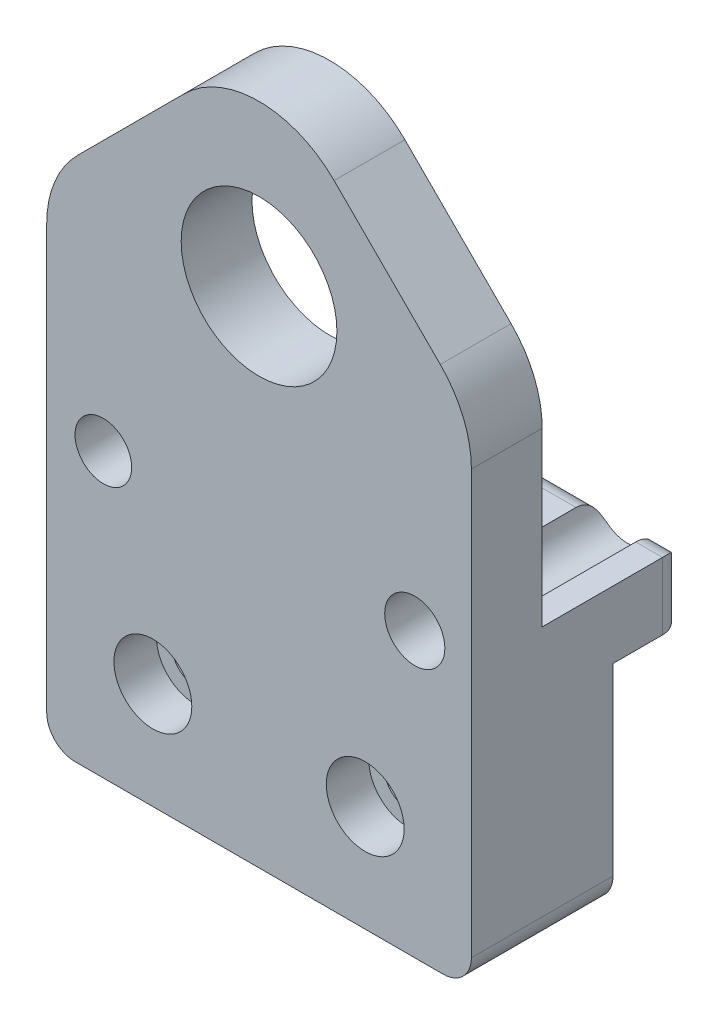
SolidWorks part; units mm, degrees
ref_plane "Front Plane" through (0, 0, 0) normal (0, 0, 1) x (1, 0, 0)
ref_plane "Top Plane" through (0, 0, 0) normal (0, 1, 0) x (1, 0, 0)
ref_plane "Right Plane" through (0, 0, 0) normal (1, 0, 0) x (0, 0, -1)
sketch "Esboço2" plane through (0, 0, 0) normal (0, 0, 1) x (1, 0, 0)
  line L0 (250, 102.2122) -> (250, 76.2122) construction
  line L1 (190, 102.2122) -> (190, 76.2122) construction
  line L2 (250, 102.2122) -> (250, 76.2122)
  line L3 (190, 102.2122) -> (190, 76.2122)
  line L4 (194, 72.2122) -> (246, 72.2122)
  line L6 (194, 172.2122) -> (246, 172.2122) construction
  line L14 (209.3934, 161.6056) -> (194.3934, 146.6056)
  line L15 (190, 76.2122) -> (190, 168.2122) construction
  line L16 (190, 135.999) -> (190, 102.2122)
  line L17 (230.6066, 161.6056) -> (245.6066, 146.6056)
  line L18 (250, 168.2122) -> (250, 76.2122) construction
  line L19 (250, 135.999) -> (250, 102.2122)
  arc A0 (190, 76.2122) -> (194, 72.2122) centre (194, 76.2122) ccw construction
  arc A1 (246, 72.2122) -> (250, 76.2122) centre (246, 76.2122) ccw construction
  arc A2 (190, 76.2122) -> (194, 72.2122) centre (194, 76.2122) ccw
  arc A3 (246, 72.2122) -> (250, 76.2122) centre (246, 76.2122) ccw
  circle A13 centre (198, 112.2122) radius 4
  circle A14 centre (198, 112.2122) radius 4
  circle A16 centre (242, 112.2122) radius 4.25
  circle A17 centre (242, 112.2122) radius 4.25
  arc A18 (209.3934, 161.6056) -> (230.6066, 161.6056) centre (220, 150.999) cw
  arc A19 (245.6066, 146.6056) -> (250, 135.999) centre (235, 135.999) cw
  circle A20 centre (220, 143.3622) radius 11
  arc A21 (194.3934, 146.6056) -> (190, 135.999) centre (205, 135.999) ccw
  point P0 (0, 0)
  point P15 (220, 172.2122)
  point P21 (220, 172.2122)
  point P29 (250, 142.2122)
  point P32 (190, 142.2122)
  dimension "D3" = 22
  dimension "D4" = 15
  dimension "D5" = 15
  dimension "D1" = 0
  dimension "D2" = 0
extrude "Ressalto-extrusão1" add sketch "Esboço2" along normal blind 20
sketch "Esboço3" plane through (0, 0, 0) normal (0, 0, -1) x (-1, 0, 0)
  line L0 (-440, 102.2122) -> (0, 102.2122) construction
  line L1 (-440, 102.2122) -> (0, 102.2122)
  line L2 (-190, 135.999) -> (-190, 76.2122) construction
  line L4 (-190, 102.2122) -> (-250, 102.2122)
  line L5 (-190, 102.2122) -> (-190, 111.6979)
  line L6 (-190, 111.6979) -> (-194.0332, 111.6979)
  line L7 (-250, 102.2122) -> (-250, 111.6979)
  line L8 (-250, 76.2122) -> (-250, 135.999) construction
  line L9 (-190, 111.6979) -> (-250, 111.6979) construction
  line L10 (-246.2188, 111.6979) -> (-250, 111.6979)
  line L11 (-201.9668, 111.6979) -> (-237.7812, 111.6979)
  circle A2 centre (-242, 112.2122) radius 4.25
  arc A3 (-246.2188, 111.6979) -> (-237.7812, 111.6979) centre (-242, 112.2122) ccw
  circle A5 centre (-198, 112.2122) radius 4
  arc A6 (-201.9668, 111.6979) -> (-194.0332, 111.6979) centre (-198, 112.2122) ccw
  line M4 (-190, 76.2122) -> (-190, 135.999)
  line M10 (-250, 135.999) -> (-250, 76.2122)
  circle M11 centre (-242, 112.2122) radius 4.25
  circle M13 centre (-198, 112.2122) radius 4
  dimension "D1" = 0
  dimension "D2" = 0
extrude "Ressalto-extrusão2" add sketch "Esboço3" along normal blind 10 contours L11 L10 L1 L6 M13 M11 M10 M4 region at (219.8748, 106.6781, 0)
fillet "Filete1" radius 3 5 edges at (192.0166, 111.6979, -10) (248.1094, 111.6979, -10) (219.874, 111.6979, -10) (250, 106.955, -10) (190, 106.955, -10)
sketch "Esboço4" plane through (0, 0, 0) normal (0, 0, -1) x (-1, 0, 0)
  line L14 (-194.0332, 111.6979) -> (-190, 111.6979)
  line L15 (-190, 111.6979) -> (-190, 135.999)
  line L16 (-194.3934, 146.6056) -> (-209.3934, 161.6056)
  line L17 (-230.6066, 161.6056) -> (-245.6066, 146.6056)
  line L18 (-250, 135.999) -> (-250, 111.6979)
  line L19 (-250, 111.6979) -> (-246.2188, 111.6979)
  line L20 (-237.7812, 111.6979) -> (-201.9668, 111.6979)
  line L21 (-194.0332, 111.6979) -> (-190, 111.6979)
  line L22 (-190, 111.6979) -> (-190, 135.999)
  line L23 (-194.3934, 146.6056) -> (-209.3934, 161.6056)
  line L24 (-230.6066, 161.6056) -> (-245.6066, 146.6056)
  line L25 (-250, 135.999) -> (-250, 111.6979)
  line L26 (-250, 111.6979) -> (-246.2188, 111.6979)
  line L27 (-237.7812, 111.6979) -> (-201.9668, 111.6979)
  arc A10 (-190, 135.999) -> (-194.3934, 146.6056) centre (-205, 135.999) ccw
  arc A11 (-209.3934, 161.6056) -> (-230.6066, 161.6056) centre (-220, 150.999) ccw
  arc A12 (-245.6066, 146.6056) -> (-250, 135.999) centre (-235, 135.999) ccw
  arc A13 (-237.7812, 111.6979) -> (-246.2188, 111.6979) centre (-242, 112.2122) ccw
  arc A14 (-194.0332, 111.6979) -> (-201.9668, 111.6979) centre (-198, 112.2122) ccw
  arc A15 (-190, 135.999) -> (-194.3934, 146.6056) centre (-205, 135.999) ccw
  arc A16 (-209.3934, 161.6056) -> (-230.6066, 161.6056) centre (-220, 150.999) ccw
  arc A17 (-245.6066, 146.6056) -> (-250, 135.999) centre (-235, 135.999) ccw
  arc A18 (-237.7812, 111.6979) -> (-246.2188, 111.6979) centre (-242, 112.2122) ccw
  arc A19 (-194.0332, 111.6979) -> (-201.9668, 111.6979) centre (-198, 112.2122) ccw
  dimension "D1" = 0
extrude "Corte-extrusão1" cut sketch "Esboço4" against normal blind 10
sketch "Esboço7" plane through (0, 0, 20) normal (0, 0, 1) x (1, 0, 0)
  circle A2 centre (235, 87.2122) radius 5.5
  circle A3 centre (235, 87.2122) radius 5.5 construction
  circle A5 centre (205, 87.2122) radius 5.5
  circle A6 centre (205, 87.2122) radius 5.5 construction
  dimension "D1" = 0
  dimension "D2" = 0
hole_wizard "Rebaixo para SHCS M61" positions "Esboço8" profile "Esboço9" counterbore size "M6" standard "Ansi Metric" end condition through all
sketch "Esboço8" plane through (0, 0, 20) normal (0, 0, 1) x (1, 0, 0)
  point P0 (235, 87.2122)
  point P3 (205, 87.2122)
sketch "Esboço9" plane through (235, 87.2122, 20) normal (1, 0, 0) x (0, -1, 0)
  line L0 (0, 0) -> (0, 30)
  line L1 (0, 30) -> (3.3, 30)
  line L3 (3.3, 30) -> (3.3, 6)
  line L4 (3.3, 6) -> (5.5, 6)
  line L5 (5.5, 6) -> (5.5, 0)
  line L7 (5.5, 0) -> (0, 0)
  line L11 (0, -6.35) -> (0, 107.95) construction
  dimension "Thru Hole Dia." = 6.6
  dimension "Thru Hole Depth" = 30
  dimension "C'Bore Dia." = 11
  dimension "C'Bore Depth" = 6
